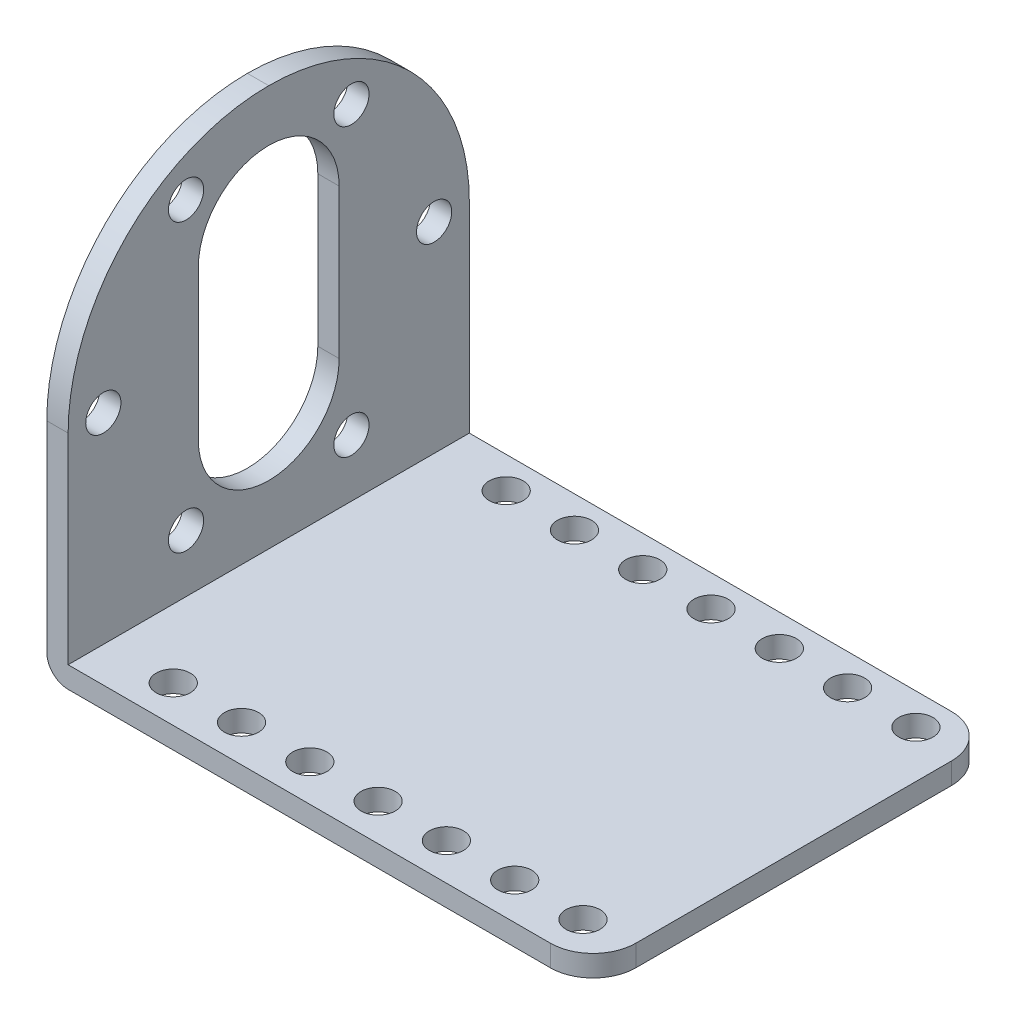
SolidWorks part; units mm, degrees
ref_plane "Front Plane" through (0, 0, 0) normal (0, 0, 1) x (1, 0, 0)
ref_plane "Top Plane" through (0, 0, 0) normal (0, 1, 0) x (1, 0, 0)
ref_plane "Right Plane" through (0, 0, 0) normal (1, 0, 0) x (0, 0, -1)
sketch "Sketch1" plane through (0, 0, 0) normal (0, 0, 1) x (1, 0, 0)
  line L0 (-8.3985, 29.3603) -> (-6.3985, 29.3603)
  line L1 (-6.3985, 29.3603) -> (-6.3985, -8.2397)
  line L2 (-6.3985, -8.2397) -> (42.8015, -8.2397)
  line L3 (42.8015, -8.2397) -> (42.8015, -10.2397)
  line L4 (42.8015, -10.2397) -> (-8.3985, -10.2397)
  line L5 (-8.3985, -10.2397) -> (-8.3985, 29.3603)
  dimension "D1" = 2
  dimension "D2" = 2
  dimension "D3" = 37.6
  dimension "D4" = 49.2
extrude "Boss-Extrude1" add sketch "Sketch1" along normal blind 37.6
sketch "Sketch2" plane through (-6.3985, 0, 0) normal (1, 0, 0) x (0, 0, -1)
  line L0 (-18.8, 29.3603) -> (-18.8, -10.686) construction
  line L1 (-37.6, 29.3603) -> (0, 29.3603) construction
  line L2 (-37.6, -10.2397) -> (0, -10.2397) construction
  line L3 (-18.8, 17.9097) -> (-18.8, 3.9097) construction
  line L4 (-12.2, 17.9097) -> (-12.2, 3.9097)
  line L5 (-25.4, 17.9097) -> (-25.4, 3.9097)
  circle A0 centre (-18.8, 10.5603) radius 15.5 construction
  circle A1 centre (-34.3, 10.5603) radius 1.65
  circle A2 centre (-26.55, 23.9837) radius 1.65
  circle A3 centre (-11.05, 23.9837) radius 1.65
  circle A4 centre (-3.3, 10.5603) radius 1.65
  circle A5 centre (-11.05, -2.8631) radius 1.65
  circle A6 centre (-26.55, -2.8631) radius 1.65
  arc A7 (-12.2, 17.9097) -> (-25.4, 17.9097) centre (-18.8, 17.9097) ccw
  arc A8 (-25.4, 3.9097) -> (-12.2, 3.9097) centre (-18.8, 3.9097) ccw
  point P22 (-18.8, 10.5603)
  point P23 (-18.8, 10.9097)
  dimension "D1" = 31
  dimension "D3" = 3.3
  dimension "D2" = 20.8
  dimension "D5" = 14
  dimension "D6" = 13.2
  dimension "D4" = 6
extrude "Cut-Extrude1" cut sketch "Sketch2" against normal through all
sketch "Sketch3" plane through (0, -8.2397, 0) normal (0, 1, 0) x (1, 0, 0)
  line L0 (42.8015, -18.5486) -> (-8.3985, -18.5486) construction
  line L1 (42.8015, -37.6) -> (42.8015, 0) construction
  line L2 (-8.3985, -37.6) -> (-8.3985, 0) construction
  circle A0 centre (0.0015, -2.9486) radius 1.6
  circle A1 centre (6.4015, -2.9486) radius 1.6
  circle A2 centre (12.8015, -2.9486) radius 1.6
  circle A3 centre (19.2015, -2.9486) radius 1.6
  circle A4 centre (25.6015, -2.9486) radius 1.6
  circle A5 centre (32.0015, -2.9486) radius 1.6
  circle A6 centre (38.4015, -2.9486) radius 1.6
  circle A7 centre (38.4015, -34.1486) radius 1.6
  circle A8 centre (32.0015, -34.1486) radius 1.6
  circle A9 centre (25.6015, -34.1486) radius 1.6
  circle A10 centre (19.2015, -34.1486) radius 1.6
  circle A11 centre (12.8015, -34.1486) radius 1.6
  circle A12 centre (6.4015, -34.1486) radius 1.6
  circle A13 centre (0.0015, -34.1486) radius 1.6
  dimension "D2" = 3.2
  dimension "D1" = 8.4
  dimension "D3" = 15.6
  dimension "D4" = 7
extrude "Cut-Extrude2" cut sketch "Sketch3" against normal through all
fillet "Fillet1" radius 18.8 2 edges at (-7.3985, 29.3603, 0) (-7.3985, 29.3603, 37.6)
fillet "Fillet2" radius 2 1 edges at (-8.3985, -10.2397, 18.8)
fillet "Fillet3" radius 4 2 edges at (42.8015, -9.2397, 37.6) (42.8015, -9.2397, 0)
